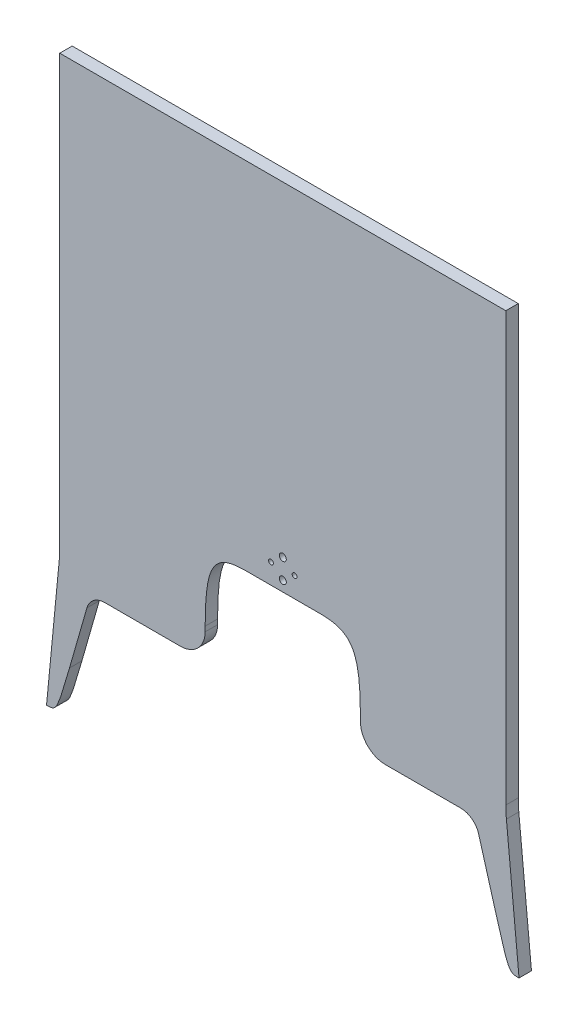
SolidWorks part; units mm, degrees
material "MDF"
ref_plane "Front Plane" through (0, 0, 0) normal (0, 0, 1) x (1, 0, 0)
ref_plane "Top Plane" through (0, 0, 0) normal (0, 1, 0) x (1, 0, 0)
ref_plane "Right Plane" through (0, 0, 0) normal (1, 0, 0) x (0, 0, -1)
sketch "Sketch1" plane through (0, 0, 0) normal (0, 0, 1) x (1, 0, 0)
  line L0 (-228.0888, 0) -> (228.0888, 0)
  line L1 (79.375, -363.22) -> (-79.375, -363.22)
  line L2 (0, -363.22) -> (0, 0) construction
  line L3 (-79.375, -363.22) -> (-79.375, -463.55)
  line L4 (196.3388, -463.55) -> (79.375, -463.55)
  line L5 (-230.9346, -584.2) -> (-196.3388, -463.55)
  line L6 (-230.9346, -584.2) -> (-241.6001, -584.2)
  line L7 (-241.6001, -584.2) -> (-228.0888, -443.879)
  line L8 (-228.0888, -443.879) -> (-228.0888, 0)
  line L9 (-196.3388, -463.55) -> (-79.375, -463.55)
  line L10 (228.0888, -443.879) -> (228.0888, 0)
  line L11 (241.6001, -584.2) -> (228.0888, -443.879)
  line L12 (230.9346, -584.2) -> (241.6001, -584.2)
  line L13 (230.9346, -584.2) -> (196.3388, -463.55)
  line L14 (79.375, -363.22) -> (79.375, -463.55)
  dimension "D1" = 363.22
  dimension "D2" = 158.75
  dimension "D3" = 106
  dimension "D4" = 31.75
  dimension "D5" = 120.65
  dimension "D6" = 174.5
  dimension "D7" = 463.55
  dimension "D8" = 140.97
extrude "Boss-Extrude1" add sketch "Sketch1" along normal blind 12.7
fillet "Fillet2" radius 69.85 1 edges at (-79.375, -363.22, 6.35) second distance 41.275 conic rho 0.6 first distance on face at (-79.375, -413.385, 6.35)
fillet "Fillet3" radius 25.4 1 edges at (-79.375, -463.55, 6.35)
fillet "Fillet4" radius 19.05 1 edges at (-196.3388, -463.55, 6.35)
ref_plane "Plane1" through (-230.9346, -584.2, 0) normal (0, 0, -1) x (-1, 0, 0)
fillet "Fillet5" radius 22.225 1 edges at (-230.9346, -584.2, 6.35) second distance 50.8 conic rho 0.7 first distance on face at (-236.2674, -584.2, 6.35)
fillet "Fillet6" radius 127 1 edges at (-228.0888, -443.879, 6.35)
sketch "Sketch3" plane through (0, 0, 12.7) normal (0, 0, 1) x (1, 0, 0)
  line L0 (0, 0) -> (0, -440.5951) construction
  line L2 (228.0888, 0) -> (-228.0888, 0) construction
  line L4 (0, 0) -> (241.6001, 0)
  line L5 (0, 0) -> (0, -584.2)
  line L6 (0, -584.2) -> (241.6001, -584.2)
  line L7 (241.6001, 0) -> (241.6001, -584.2)
  point P3 (0, 0)
extrude "Cut-Extrude1" cut sketch "Sketch3" against normal up to next
mirror "Mirror5" about plane through (0, 0, -0.3502) normal (-1, 0, 0) of bodies 103
hole_wizard "1/4 Clearance Hole1" positions "Sketch6" profile "Sketch7" hole size "1/4" standard "ANSI Inch" end condition up to next
sketch "Sketch6" plane through (0, 0, 12.7) normal (0, 0, 1) x (1, 0, 0)
  circle A0 centre (0, -352.7425) radius 4.8412 construction
  circle A1 centre (0, -332.4225) radius 4.8412 construction
  point P0 (0, -332.4225)
  point P2 (0, -352.7425)
sketch "Sketch7" plane through (0, -332.4225, 12.7) normal (1, 0, 0) x (0, -1, 0)
  line L0 (0, 0) -> (0, 12.7)
  line L1 (0, 12.7) -> (3.5712, 12.7)
  line L2 (3.5712, 12.7) -> (3.5712, 0)
  line L5 (3.5712, 0) -> (0, 0)
  line L11 (0, -6.35) -> (0, 107.95) construction
  dimension "Thru Hole Dia." = 7.1425
  dimension "Thru Hole Depth" = 12.7
hole_wizard "#8 Clearance Hole1" positions "Sketch8" profile "Sketch9" hole size "#8" standard "ANSI Inch" end condition up to next
sketch "Sketch8" plane through (0, 0, 12.7) normal (0, 0, 1) x (1, 0, 0)
  arc A0 (11.4694, -341.1379) -> (12.685, -341.1379) centre (12.0772, -342.5825) ccw construction
  arc A1 (-12.9267, -341.2655) -> (-11.7296, -341.0543) centre (-12.0772, -342.5825) ccw construction
  point P0 (-12.0772, -342.5825)
  point P2 (12.0772, -342.5825)
sketch "Sketch9" plane through (-12.0772, -342.5825, 12.7) normal (1, 0, 0) x (0, -1, 0)
  line L0 (0, 0) -> (0, 12.7)
  line L1 (0, 12.7) -> (2.4574, 12.7)
  line L2 (2.4574, 12.7) -> (2.4574, 0)
  line L5 (2.4574, 0) -> (0, 0)
  line L11 (0, -6.35) -> (0, 107.95) construction
  dimension "Thru Hole Dia." = 4.9149
  dimension "Thru Hole Depth" = 12.7
